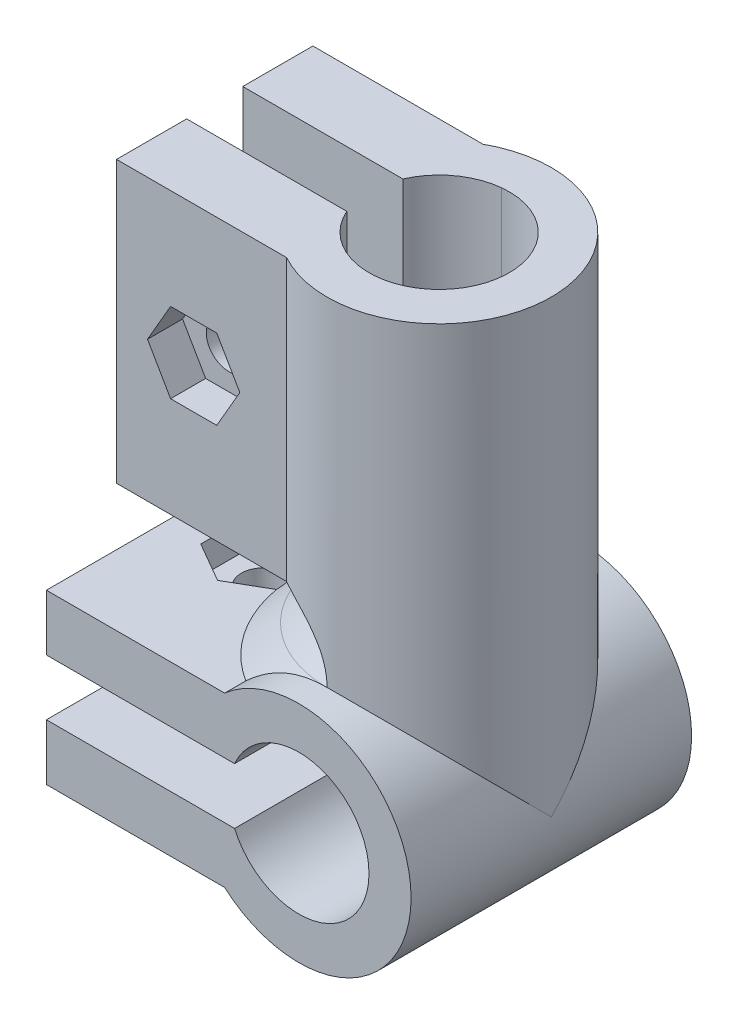
SolidWorks part; units mm, degrees
material "ABS"
ref_plane "Płaszczyzna przednia" through (0, 0, 0) normal (0, 0, 1) x (1, 0, 0)
ref_plane "Płaszczyzna górna" through (0, 0, 0) normal (0, 1, 0) x (1, 0, 0)
ref_plane "Płaszczyzna prawa" through (0, 0, 0) normal (1, 0, 0) x (0, 0, -1)
sketch "Szkic1" plane through (0, 0, 0) normal (0, 0, 1) x (1, 0, 0)
  line L0 (0, -6.1) -> (0, -10.1) construction
  line L1 (0, -8.1) -> (-18, -8.1) construction
  line L2 (-4.5826, -10.1) -> (-18, -10.1)
  line L3 (-18, -10.1) -> (-18, -14.1)
  line L4 (-4.5826, -6.1) -> (-18, -6.1)
  line L5 (-18, -6.1) -> (-18, -2.1)
  line L8 (0, -6.1) -> (-4.5826, -6.1) construction
  line L9 (0, -10.1) -> (-4.5826, -10.1) construction
  line L10 (0, -14.9326) -> (0, -7.9854) construction
  line L11 (0, 0) -> (0, -8.1) construction
  line L12 (-18, -2.1) -> (-5.2915, -2.1)
  line L13 (-18, -14.1) -> (-5.2915, -14.1)
  arc A0 (-4.5826, -10.1) -> (-4.5826, -6.1) centre (0, -8.1) ccw
  arc A1 (-5.2915, -14.1) -> (-5.2915, -2.1) centre (0, -8.1) ccw
  arc A2 (-8, -8.1) -> (-7.746, -10.1) centre (0, -8.1) ccw construction
  arc A3 (-5, -8.1) -> (-4.5826, -10.1) centre (0, -8.1) ccw construction
  arc A4 (-7.746, -6.1) -> (-8, -8.1) centre (0, -8.1) ccw construction
  arc A5 (-4.5826, -6.1) -> (-5, -8.1) centre (0, -8.1) ccw construction
  arc A6 (-7.746, -10.1) -> (-5.2915, -14.1) centre (0, -8.1) ccw construction
  arc A7 (-5.2915, -2.1) -> (-7.746, -6.1) centre (0, -8.1) ccw construction
  point P7 (0, -8.1)
  point P23 (0, -8.1)
  dimension "D1" = 10
  dimension "D3" = 4
  dimension "D4" = 18
  dimension "D5" = 270
  dimension "D6" = 8.1
  dimension "D7" = 4
  dimension "D8" = 4
extrude "Dodanie-wyciągnięcie1" add sketch "Szkic1" along normal blind 10 and the other way blind 10
sketch "Szkic3" plane through (0, 0, 0) normal (0, 1, 0) x (1, 0, 0)
  line L0 (0, 0) -> (-4.4965, 0) construction
  circle A0 centre (0, 0) radius 8
  circle A1 centre (0, 0) radius 5
  dimension "D1" = 16
  dimension "D2" = 10
extrude "Dodanie-wyciągnięcie2" add sketch "Szkic3" along normal blind 2 and the other way up to next contours A1 | A0 A1 | A1 | A0 region at (-7.7737, 0, 0) region at (0, 0, 0)
extrude "Wytnij-wyciągnięcie7" cut sketch "Szkic3<3>" along normal up to next contours A1 region at (0, 0, 0)
sketch "Szkic3<3>" plane through (0, 0, 0) normal (0, 1, 0) x (1, 0, 0) same geometry as "Szkic3"
ref_plane "Płaszczyzna2" through (0, 2, 0) normal (0, 1, 0) x (1, 0, 0)
sketch "Szkic4" plane through (0, 2, 0) normal (0, 1, 0) x (1, 0, 0)
  line L0 (0, 8) -> (0, 5)
  line L1 (0, 5) -> (0, -5) construction
  line L2 (0, -5) -> (0, -8)
  arc A0 (0, -8) -> (0, 8) centre (0, 0) ccw
  arc A1 (0, -5) -> (0, 5) centre (0, 0) ccw
  arc A2 (0, 8) -> (0, -8) centre (0, 0) ccw construction
  arc A3 (0, 5) -> (0, -5) centre (0, 0) ccw construction
  point P9 (0, 0)
  dimension "D1" = 10
  dimension "D3" = 16
extrude "Dodanie-wyciągnięcie4" add sketch "Szkic4" along normal blind 2
ref_plane "Płaszczyzna3" through (0, 4, 0) normal (0, 1, 0) x (1, 0, 0)
sketch "Szkic5" plane through (0, 4, 0) normal (0, 1, 0) x (1, 0, 0)
  line L0 (-5, 0) -> (-16, 0) construction
  line L1 (0, -2) -> (0, 2) construction
  line L2 (-4.5826, 2) -> (-16, 2)
  line L3 (-16, 2) -> (-16, 7)
  line L5 (-4.5826, -2) -> (-16, -2)
  line L6 (-16, -2) -> (-16, -7)
  line L8 (0, 2) -> (-4.5826, 2) construction
  line L9 (0, 0) -> (-5, 0) construction
  line L10 (0, -2) -> (-4.5826, -2) construction
  line L13 (-16, 7) -> (-3.873, 7)
  line L14 (-16, -7) -> (-3.873, -7)
  arc A0 (-4.5826, -2) -> (-4.5826, 2) centre (0, 0) ccw
  arc A1 (-3.873, -7) -> (-3.873, 7) centre (0, 0) ccw
  arc A2 (-7.746, 2) -> (-8, 0) centre (0, 0) ccw construction
  arc A3 (-8, 0) -> (-7.746, -2) centre (0, 0) ccw construction
  arc A6 (-5, 0) -> (-4.5826, -2) centre (0, 0) ccw construction
  arc A7 (-4.5826, 2) -> (-5, 0) centre (0, 0) ccw construction
  arc A8 (-3.873, -7) -> (0, -8) centre (0, 0) ccw construction
  arc A9 (0, 8) -> (-3.873, 7) centre (0, 0) ccw construction
  arc A10 (-3.873, 7) -> (-7.746, 2) centre (0, 0) ccw construction
  arc A11 (-3.873, 7) -> (-7.746, 2) centre (0, 0) ccw construction
  arc A12 (-7.746, -2) -> (-3.873, -7) centre (0, 0) ccw construction
  arc A13 (-7.746, -2) -> (-3.873, -7) centre (0, 0) ccw construction
  point P8 (0, 0)
  dimension "D1" = 10
  dimension "D3" = 16
  dimension "D2" = 16
  dimension "D4" = 4
  dimension "D5" = 5
  dimension "D6" = 5
extrude "Dodanie-wyciągnięcie5" add sketch "Szkic5" along normal blind 20
chamfer "Sfazowanie2" distance 2.1 angle 45 1 edges at (-8, 2, 0)
chamfer "Sfazowanie3" distance 2 angle 45 1 edges at (-8, -2.1, 0)
fillet "Zaokrąglenie1" radius 4 2 edges at (0, 4, -6.5) (0, 4, 6.5)
sketch "Szkic6" plane through (0, 0, -7) normal (0, 0, -1) x (-1, 0, 0)
  line L0 (16, 14) -> (10.5, 14)
  line L1 (16, 24) -> (16, 4) construction
  circle A0 centre (10.5, 14) radius 1.6
  dimension "D2" = 3.2
  dimension "D1" = 5.5
extrude "Wytnij-wyciągnięcie1" cut sketch "Szkic6" against normal up to surface (14 mm away) contours A0 region at (-8.9453, 14, -7) up to face at (-8.7492, 11.9997, 7)
sketch "Szkic7" plane through (0, 0, 7) normal (0, 0, 1) x (1, 0, 0)
  line L1 (-13.7909, 14) -> (-12.1454, 11.15)
  line L2 (-12.1454, 11.15) -> (-8.8546, 11.15)
  line L3 (-8.8546, 11.15) -> (-7.2091, 14)
  line L4 (-7.2091, 14) -> (-8.8546, 16.85)
  line L5 (-8.8546, 16.85) -> (-12.1454, 16.85)
  line L6 (-12.1454, 16.85) -> (-13.7909, 14)
  circle A0 centre (-10.5, 14) radius 2.85 construction
  dimension "D1" = 5.7
extrude "Wytnij-wyciągnięcie2" cut sketch "Szkic7" against normal blind 2.5
sketch "Szkic8" plane through (0, 0, -7) normal (0, 0, -1) x (-1, 0, 0)
  circle A0 centre (10.5, 14) radius 2.85
  dimension "D1" = 5.7
extrude "Wytnij-wyciągnięcie3" cut sketch "Szkic8" against normal blind 2.5
sketch "Szkic9" plane through (0, -14.1, 0) normal (0, -1, 0) x (1, 0, 0)
  line L0 (-18, 0) -> (-12.5, 0) construction
  line L1 (-18, -10) -> (-18, 10) construction
  circle A0 centre (-12.5, 0) radius 1.6
  dimension "D2" = 3.2
  dimension "D1" = 5.5
extrude "Wytnij-wyciągnięcie4" cut sketch "Szkic9" against normal up to surface (12 mm away) up to face at (-10.3124, -2.1, 0)
sketch "Szkic11" plane through (0, -2.1, 0) normal (0, 1, 0) x (1, 0, 0)
  line L1 (-12.5, 3.2909) -> (-15.35, 1.6454)
  line L2 (-15.35, 1.6454) -> (-15.35, -1.6454)
  line L3 (-15.35, -1.6454) -> (-12.5, -3.2909)
  line L4 (-12.5, -3.2909) -> (-9.65, -1.6454)
  line L5 (-9.65, -1.6454) -> (-9.65, 1.6454)
  line L6 (-9.65, 1.6454) -> (-12.5, 3.2909)
  circle A0 centre (-12.5, 0) radius 2.85 construction
  point P1 (-9.65, 0)
  dimension "D1" = 5.7
extrude "Wytnij-wyciągnięcie5" cut sketch "Szkic11" against normal blind 2 and the other way up to next
sketch "Szkic12" plane through (0, -14.1, 0) normal (0, -1, 0) x (1, 0, 0)
  circle A0 centre (-12.5, 0) radius 2.85
  dimension "D1" = 5.7
extrude "Wytnij-wyciągnięcie6" cut sketch "Szkic12" against normal blind 2
equation "\"SkidsDiameter\"=10"
equation "\"D1@Szkic1\"=\"SkidsDiameter\""
equation "\"Tolerance\"= 0.1"
equation "\"WallThickness\"=3"
equation "\"D2@Szkic1\"=\"WallThickness\""
equation "\"SkidsScrewGap\"=4"
equation "\"D3@Szkic1\"=\"SkidsScrewGap\""
equation "\"SkidsScrewLength\"= 10"
equation "\"D4@Szkic1\"=\"SkidsScrewLength\"+\"SkidsDiameter\"/2+\"WallThickness\""
equation "\"ChassisDiameter\"=10"
equation "\"SkidsScrewAngle\"= 270"
equation "\"D5@Szkic1\"=\"SkidsScrewAngle\""
equation "\"D6@Szkic1\"=\"SkidsDiameter\"/2+\"WallThickness\"+0.1"
equation "\"D1@Dodanie-wyciągnięcie2\"=\"WallThickness\""
equation "\"D1@Szkic4\"=\"ChassisDiameter\""
equation "\"D2@Szkic4\"=\"WallThickness\""
equation "\"D3@Szkic4\"=\"ChassisDiameter\"+\"WallThickness\"*2"
equation "\"D1@Szkic5\"=\"ChassisDiameter\""
equation "\"D2@Szkic5\"=\"ChassisDiameter\"+\"WallThickness\"*2"
equation "\"ChassisScrewLength\"= 8"
equation "\"D3@Szkic5\"=\"ChassisScrewLength\"+\"ChassisDiameter\"/2+\"WallThickness\""
equation "\"ChassisScrewGap\"=4"
equation "\"D4@Szkic5\"=\"ChassisScrewGap\""
equation "\"2.8.00mm\"=3"
equation "\"ChassisScrewWallThickness\"=5"
equation "\"D6@Szkic5\"=\"ChassisScrewWallThickness\""
equation "\"D5@Szkic5\"=\"ChassisScrewWallThickness\""
equation "\"SkidsScrewWallThickness\"=4"
equation "\"D7@Szkic1\"=\"SkidsScrewWallThickness\""
equation "\"D1@Szkic6\"=\"ChassisScrewLength\"/2 +\"WallThickness\"/2"
equation "\"D1@Szkic7\"=5.5+ \"Tolerance\"*2"
equation "\"D1@Wytnij-wyciągnięcie2\"=\"ChassisScrewWallThickness\"/2"
equation "\"D2@Szkic6\"=3+\"Tolerance\"*2"
equation "\"D1@Szkic8\"=5.5+\"Tolerance\"*2"
equation "\"D1@Wytnij-wyciągnięcie3\"=\"ChassisScrewWallThickness\"/2"
equation "\"D1@Szkic9\"=\"ChassisScrewLength\"/2 +\"WallThickness\"/2"
equation "\"D2@Szkic9\"=3+\"Tolerance\"*2"
equation "\"D1@Szkic11\"=5.5+\"Tolerance\"*2"
equation "\"D1@Wytnij-wyciągnięcie5\"=\"SkidsScrewWallThickness\"/2"
equation "\"D1@Szkic12\"=5.5+\"Tolerance\"*2"
equation "\"D1@Wytnij-wyciągnięcie6\"=\"SkidsScrewWallThickness\"/2"
equation "\"D1@Szkic3\"=\"ChassisDiameter\"+\"WallThickness\"*2"
equation "\"D2@Szkic3\"=\"ChassisDiameter\""
